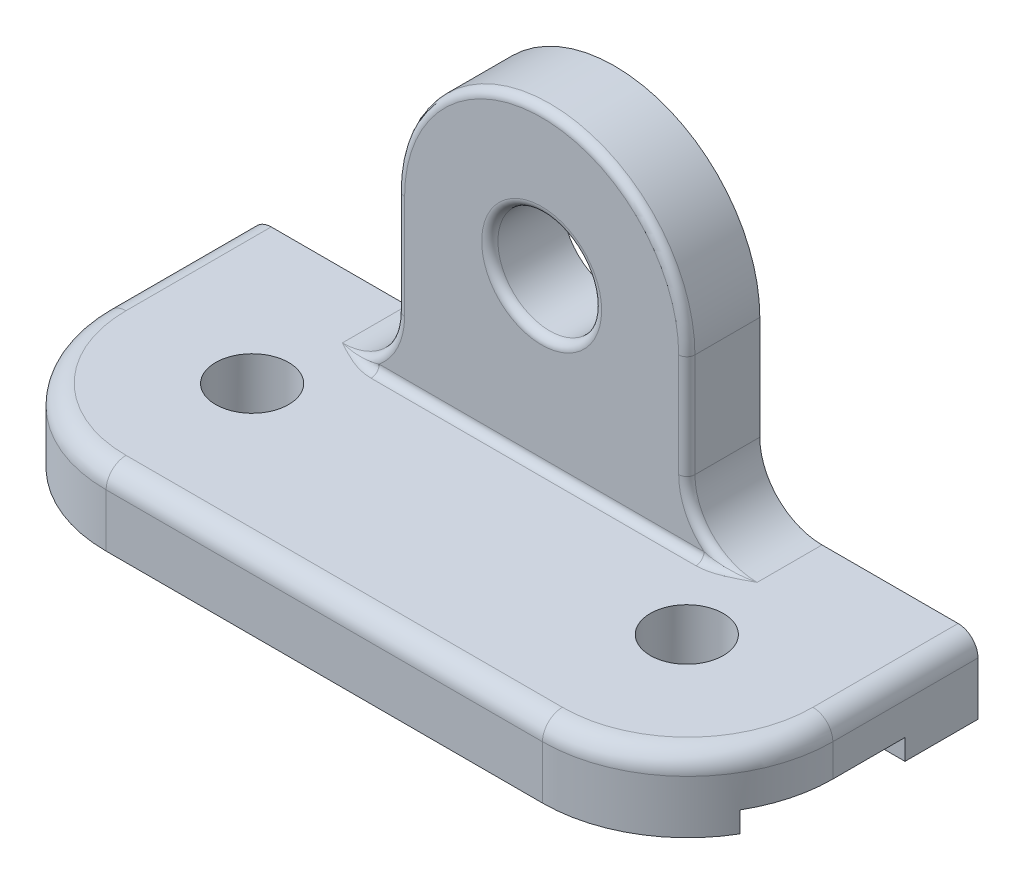
SolidWorks part; units mm, degrees
ref_plane "Front Plane" through (0, 0, 0) normal (0, 0, 1) x (1, 0, 0)
ref_plane "Top Plane" through (0, 0, 0) normal (0, 1, 0) x (1, 0, 0)
ref_plane "Right Plane" through (0, 0, 0) normal (1, 0, 0) x (0, 0, -1)
sketch "Sketch2" plane through (0, 0, 0) normal (0, 1, 0) x (1, 0, 0)
  line L1 (-55.626, 0) -> (55.626, 0)
  line L2 (-55.626, 0) -> (-55.626, -44.45)
  line L3 (-55.626, -44.45) -> (55.626, -44.45)
  line L4 (55.626, 0) -> (55.626, -44.45)
  dimension "D1" = 111.252
  dimension "D2" = 44.45
  dimension "D3" = 55.626
  dimension "D4" = 44.45
extrude "Boss-Extrude1" add sketch "Sketch2" along normal blind 11.176
fillet "Fillet1" radius 22.225 1 edges at (-55.626, 5.588, 44.45)
fillet "Fillet2" radius 22.225 1 edges at (55.626, 5.588, 44.45)
sketch "Sketch4" plane through (0, 0, 0) normal (0, 0, 1) x (1, 0, 0)
  line L0 (0, 11.176) -> (0, 36.576) construction
  line L1 (-33.401, 11.176) -> (33.401, 11.176) construction
  line L2 (22.225, 36.576) -> (22.225, 11.176)
  line L3 (-22.225, 36.576) -> (-22.225, 11.176)
  line L5 (-22.225, 11.176) -> (22.225, 11.176)
  arc A0 (22.225, 36.576) -> (-22.225, 36.576) centre (0, 36.576) ccw
  circle A1 centre (0, 36.576) radius 7.9375
  dimension "D1" = 25.4
fillet "Fillet5" radius 3.048 5 edges at (-55.626, 11.176, 11.1125) (-49.1164, 11.176, 37.9404) (0, 11.176, 44.45) (49.1164, 11.176, 37.9404) (55.626, 11.176, 11.1125)
ref_plane "Plane1" through (-55.626, 0, 0) normal (-1, 0, 0) x (0, 0, 1)
sketch "Sketch8" plane through (-55.626, 0, 0) normal (-1, 0, 0) x (0, 0, 1)
  line L0 (0, 0) -> (22.225, 0) construction
  line L1 (22.225, 0) -> (44.45, 0) construction
  line L2 (11.176, 0) -> (22.225, 0)
  line L3 (22.225, 0) -> (33.401, 0)
  line L5 (11.176, 0) -> (11.176, 3.175)
  line L6 (11.176, 3.175) -> (33.401, 3.175)
  line L7 (33.401, 3.175) -> (33.401, 0)
  line L8 (0, 8.128) -> (0, 0) construction
  dimension "D1" = 3.175
  dimension "D2" = 22.225
  dimension "D3" = 11.176
extrude "Cut-Extrude3" cut sketch "Sketch8" against normal through all contours L3 L7 L6 L5 L2
sketch "Sketch9" plane through (0, 11.176, 0) normal (0, 1, 0) x (1, 0, 0)
  line L0 (0, -24.4475) -> (0, 24.4475) construction
  line L1 (52.578, 0) -> (-52.578, 0) construction
  circle A0 centre (-33.274, -22.225) radius 5.588
  dimension "D1" = 33.274
  dimension "D2" = 22.225
extrude "Cut-Extrude4" cut sketch "Sketch9" against normal through all both and the other way through all
mirror "Mirror1" about plane through (0, 0, 0) normal (1, 0, 0) of "Cut-Extrude4"
sketch "Sketch10" plane through (0, 0, 0) normal (0, 0, -1) x (-1, 0, 0)
extrude "Boss-Extrude3" add sketch "Sketch4" along normal blind 11.176
fillet "Fillet8" radius 9.525 2 edges at (22.225, 11.176, 5.588) (-22.225, 11.176, 5.588)
fillet "Fillet9" radius 1.2446 6 edges at (-25.0148, 13.9658, 11.176) (-22.225, 28.6385, 11.176) (0, 58.801, 11.176) (22.225, 28.6385, 11.176) (25.0148, 13.9658, 11.176) (0, 11.176, 11.176)
fillet "Fillet10" radius 1.2446 1 edges at (7.9375, 36.576, 11.176)
